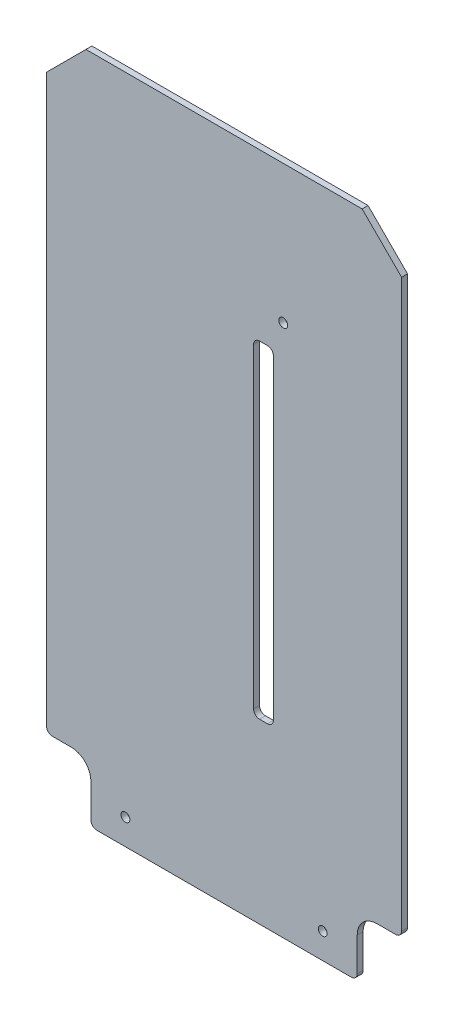
SolidWorks part; units mm, degrees
ref_plane "Plan de face" through (0, 0, 0) normal (0, 0, 1) x (1, 0, 0)
ref_plane "Plan de dessus" through (0, 0, 0) normal (0, 1, 0) x (1, 0, 0)
ref_plane "Plan de droite" through (0, 0, 0) normal (1, 0, 0) x (0, 0, -1)
sketch "Esquisse1" plane through (0, 0, 0) normal (0, 0, 1) x (1, 0, 0)
  line L1 (0, 0) -> (180, 0)
  line L2 (0, 0) -> (0, 340)
  line L3 (0, 340) -> (180, 340)
  line L4 (180, 0) -> (180, 340)
  dimension "D1" = 180
  dimension "D2" = 340
extrude "Boss.-Extru.1" add sketch "Esquisse1" along normal blind 3
sketch "Esquisse2" plane through (0, 0, 3) normal (0, 0, 1) x (1, 0, 0)
  line L0 (0, 13) -> (180, 13) construction
  line L1 (0, 340) -> (0, 0) construction
  line L2 (180, 0) -> (180, 340) construction
  line L3 (0, 0) -> (180, 0) construction
  circle A0 centre (40, 13) radius 2.25
  circle A1 centre (140, 13) radius 2.25
  dimension "D1" = 4.5
  dimension "D3" = 40
  dimension "D4" = 100
  dimension "D2" = 13
extrude "Enlèv. mat.-Extru.1" cut sketch "Esquisse2" against normal through all both and the other way through all
sketch "Esquisse3" plane through (0, 0, 3) normal (0, 0, 1) x (1, 0, 0)
  line L1 (0, 0) -> (22.5, 0)
  line L2 (0, 0) -> (0, 30)
  line L3 (0, 30) -> (22.5, 30)
  line L4 (22.5, 0) -> (22.5, 30)
  line L5 (180, 0) -> (157.5, 0)
  line L6 (180, 0) -> (180, 30)
  line L7 (180, 30) -> (157.5, 30)
  line L8 (157.5, 0) -> (157.5, 30)
  dimension "D1" = 30
  dimension "D2" = 22.5
  dimension "D3" = 22.5
extrude "Enlèv. mat.-Extru.2" cut sketch "Esquisse3" against normal through all both and the other way through all
fillet "Congé1" radius 10 2 edges at (157.5, 30, 1.5) (22.5, 30, 1.5)
fillet "Congé2" radius 3 4 edges at (0, 30, 1.5) (22.5, 0, 1.5) (180, 30, 1.5) (157.5, 0, 1.5)
sketch "Esquisse4" plane through (0, 0, 3) normal (0, 0, 1) x (1, 0, 0)
  line L0 (0, 340) -> (0, 33) construction
  line L1 (105, 256) -> (115, 256)
  line L2 (105, 256) -> (105, 90)
  line L3 (105, 90) -> (115, 90)
  line L4 (115, 256) -> (115, 90)
  line L5 (25.5, 0) -> (154.5, 0) construction
  dimension "D1" = 105
  dimension "D2" = 10
  dimension "D3" = 90
  dimension "D4" = 166
extrude "Enlèv. mat.-Extru.3" cut sketch "Esquisse4" against normal through all both and the other way through all
fillet "Congé3" radius 3 4 edges at (105, 256, 1.5) (115, 256, 1.5) (115, 90, 1.5) (105, 90, 1.5)
chamfer "Chanfrein1" distance 20 angle 45 1 edges at (180, 340, 1.5)
chamfer "Chanfrein2" distance 20 angle 45 1 edges at (0, 340, 1.5)
sketch "Esquisse5" plane through (0, 0, 3) normal (0, 0, 1) x (1, 0, 0)
  line L0 (180, 270) -> (120, 270) construction
  line L1 (180, 33) -> (180, 320) construction
  line L2 (25.5, 0) -> (154.5, 0) construction
  circle A0 centre (120, 270) radius 2.25
  dimension "D2" = 4.5
  dimension "D1" = 60
  dimension "D3" = 270
extrude "Enlèv. mat.-Extru.4" cut sketch "Esquisse5" against normal through all
